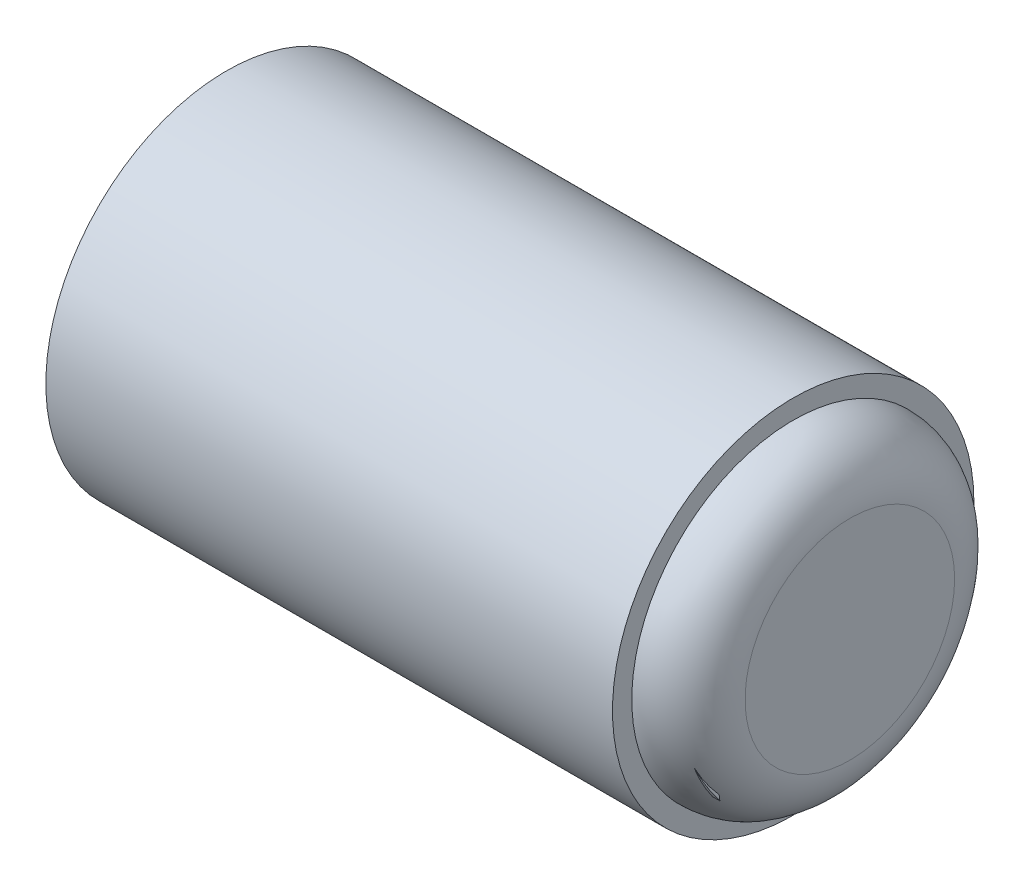
SolidWorks part; units mm, degrees
ref_plane "Front Plane" through (0, 0, 0) normal (0, 0, 1) x (1, 0, 0)
ref_plane "Top Plane" through (0, 0, 0) normal (0, 1, 0) x (1, 0, 0)
ref_plane "Right Plane" through (0, 0, 0) normal (1, 0, 0) x (0, 0, -1)
sketch "Sketch2" plane through (0, 0, 0) normal (1, 0, 0) x (0, 0, -1)
  circle A0 centre (0, 0) radius 3.1894
  circle A1 centre (0, 0) radius 2.5893
extrude "Boss-Extrude1" add sketch "Sketch2" along normal blind 10
sketch "Sketch3" plane through (10, 0, 0) normal (1, 0, 0) x (0, 0, -1)
  circle A0 centre (0, 0) radius 2.849
extrude "Boss-Extrude2" add sketch "Sketch3" along normal blind 1
fillet "Fillet1" radius 1 1 edges at (11, 0, -2.849)
sketch "Sketch5" plane through (0, 0, 0) normal (-1, 0, 0) x (0, 0, 1)
  circle A0 centre (0, 0) radius 2.5893 construction
  circle A1 centre (0, 0) radius 2.5893
curve "Helix/Spiral1" pitch 3 height 9.3 radius 2.5893 centre (0, 0, 0) axis (1, 0, 0) start towards (0, 0, 1)
sketch "Sketch6" plane through (11, 0, 0) normal (1, 0, 0) x (0, 0, -1)
  circle A0 centre (0, 0) radius 1.2989
extrude "Cut-Extrude1" [suppressed] cut sketch "Sketch6" against normal blind 1
sketch "Sketch7" plane through (0, 0, 0) normal (0, 1, 0) x (1, 0, 0)
  line L0 (0, -2.5893) -> (1.5, -2.5893)
  line L1 (0, -2.5893) -> (10, -2.5893) construction
  line L2 (1.5, -2.5893) -> (1.2, -2.2893)
  line L3 (1.2, -2.2893) -> (0.3, -2.2893)
  line L4 (0.3, -2.2893) -> (0, -2.5893)
  dimension "D1" = 135
  dimension "D2" = 135
  dimension "D3" = 1.5
  dimension "D4" = 0.3
sweep "Sweep1" add profiles "Sketch7" path "Helix/Spiral1"
